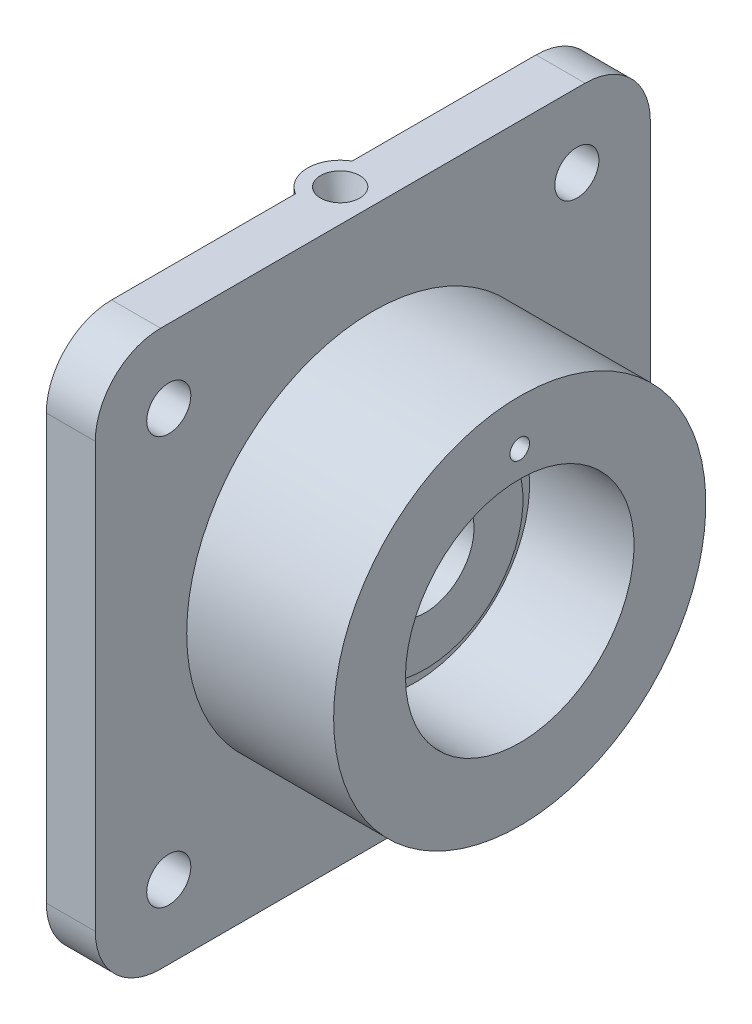
SolidWorks part; units mm, degrees
material "1060 Сплав"
ref_plane "Спереди" through (0, 0, 0) normal (0, 0, 1) x (1, 0, 0)
ref_plane "Сверху" through (0, 0, 0) normal (0, 1, 0) x (1, 0, 0)
ref_plane "Справа" through (0, 0, 0) normal (1, 0, 0) x (0, 0, -1)
sketch "Эскиз1" plane through (0, 0, 0) normal (0, 0, 1) x (1, 0, 0)
  line L0 (-987.0334, 0) -> (48364.6386, 0) construction
  line L1 (0, -987.0334) -> (0, 48364.6386) construction
  line L2 (0, -15) -> (0, -25)
  line L3 (0, -25) -> (20, -28.5265)
  line L4 (20, -28.5265) -> (20, -57)
  line L5 (20, -57) -> (80, -57)
  line L6 (80, -57) -> (80, -35)
  line L7 (80, -35) -> (48, -35)
  line L8 (48, -35) -> (48, -30)
  line L9 (48, -30) -> (51, -30)
  line L10 (51, -30) -> (51, -15)
  line L11 (51, -15) -> (39, -15)
  line L12 (39, -15) -> (39, -20)
  line L13 (39, -20) -> (34, -20)
  line L14 (34, -20) -> (34, -15)
  line L15 (34, -15) -> (29, -15)
  line L16 (29, -15) -> (29, -20)
  line L17 (29, -20) -> (24, -20)
  line L18 (24, -20) -> (24, -15)
  line L19 (24, -15) -> (0, -15)
  dimension "D1" = 5
  dimension "D2" = 24
  dimension "D3" = 15
  dimension "D4" = 5
  dimension "D5" = 12
  dimension "D6" = 60
  dimension "D7" = 3
  dimension "D8" = 70
  dimension "D9" = 114
  dimension "D10" = 80
  dimension "D11" = 60
  dimension "D12" = 10
  dimension "D13" = 25
revolve "Повернуть1" add sketch "Эскиз1" angle 360 about L0
sketch "Эскиз2" plane through (20, 0, 0) normal (-1, 0, 0) x (0, 0, 1)
  line L1 (-65, -85) -> (65, -85)
  line L2 (-85, -65) -> (-85, 65)
  line L3 (-65, 85) -> (65, 85)
  line L4 (85, -65) -> (85, 65)
  line L5 (-85, -85) -> (85, 85) construction
  line L6 (-85, 85) -> (85, -85) construction
  arc A0 (-65, -85) -> (-85, -65) centre (-65, -65) cw
  arc A1 (85, -65) -> (65, -85) centre (65, -65) cw
  arc A2 (65, 85) -> (85, 65) centre (65, 65) cw
  arc A3 (-65, 85) -> (-85, 65) centre (-65, 65) ccw
  circle A4 centre (-62.5, -62.5) radius 6.75
  circle A5 centre (-62.5, 62.5) radius 6.75
  circle A6 centre (62.5, 62.5) radius 6.75
  circle A7 centre (62.5, -62.5) radius 6.75
  circle A8 centre (0, 0) radius 20
  point P0 (0, 0)
  point P29 (0, 0)
  dimension "D2" = 20
  dimension "D3" = 13.5
  dimension "D6" = 40
  dimension "D1" = 170
  dimension "D4" = 62.5
  dimension "D5" = 4
extrude "Бобышка-Вытянуть1" add sketch "Эскиз2" against normal blind 15
sketch "Эскиз3" plane through (0, 85, 0) normal (0, 1, 0) x (1, 0, 0)
  line L0 (-1000, 0) -> (49000, 0) construction
  line L1 (35, -65) -> (35, 65) construction
  circle A0 centre (25, 0) radius 10
  dimension "D1" = 20
extrude "Бобышка-Вытянуть2" add sketch "Эскиз3" against normal up to next
sketch "Эскиз4" plane through (0, 85, 0) normal (0, 1, 0) x (1, 0, 0)
  circle A0 centre (25, 0) radius 6
  dimension "D1" = 12
ref_plane "Плоскость1" through (0, 73, 0) normal (0, 1, 0) x (1, 0, 0)
sketch "Эскиз5" plane through (0, 73, 0) normal (0, 1, 0) x (1, 0, 0)
  circle A2 centre (25, 0) radius 3
  circle A3 centre (25, 0) radius 3
  dimension "D1" = 3
loft "Вырез-По сечениям1" cut profiles "Эскиз5", "Эскиз4" connector at (25.7734, 73, -2.8986) connector at (23.0458, 85, -5.6728)
sketch "Эскиз6" plane through (0, 73, 0) normal (0, 1, 0) x (1, 0, 0)
  line L0 (0, 25) -> (0, -25) construction
  line L2 (-1000, 0) -> (49000, 0) construction
  circle A0 centre (25, 0) radius 3
  dimension "D1" = 6
  dimension "D2" = 25
extrude "Вырез-Вытянуть1" cut sketch "Эскиз6" against normal blind 33
sketch "Эскиз8" plane through (80, 0, 0) normal (1, 0, 0) x (0, 0, -1)
  line L0 (0, -1000) -> (0, 49000) construction
  line L1 (-65, 85) -> (65, 85) construction
  circle A0 centre (0, 43) radius 3
  dimension "D1" = 6
  dimension "D2" = 42
extrude "Вырез-Вытянуть2" cut sketch "Эскиз8" against normal blind 58
sketch "Эскиз10" plane through (0, 40, 0) normal (0, 1, 0) x (1, 0, 0)
  line L0 (25, 3) -> (25, 4.5)
  line L1 (25, -3) -> (25, -4.5)
  arc A0 (25, 3) -> (25, -3) centre (25, 0) ccw
  arc A1 (25, 4.5) -> (25, -4.5) centre (25, 0) ccw
  dimension "D1" = 6
  dimension "D2" = 9
extrude "Бобышка-Вытянуть3" add sketch "Эскиз10" along normal blind 6
sketch "Эскиз11" plane through (80, 0, 0) normal (1, 0, 0) x (0, 0, -1)
  line L0 (3, 43) -> (4.5, 43)
  line L1 (-3, 43) -> (-4.5, 43)
  arc A0 (-3, 43) -> (3, 43) centre (0, 43) ccw
  arc A1 (-4.5, 43) -> (4.5, 43) centre (0, 43) ccw
  dimension "D1" = 6
  dimension "D2" = 9
extrude "Бобышка-Вытянуть4" add sketch "Эскиз11" against normal blind 58
